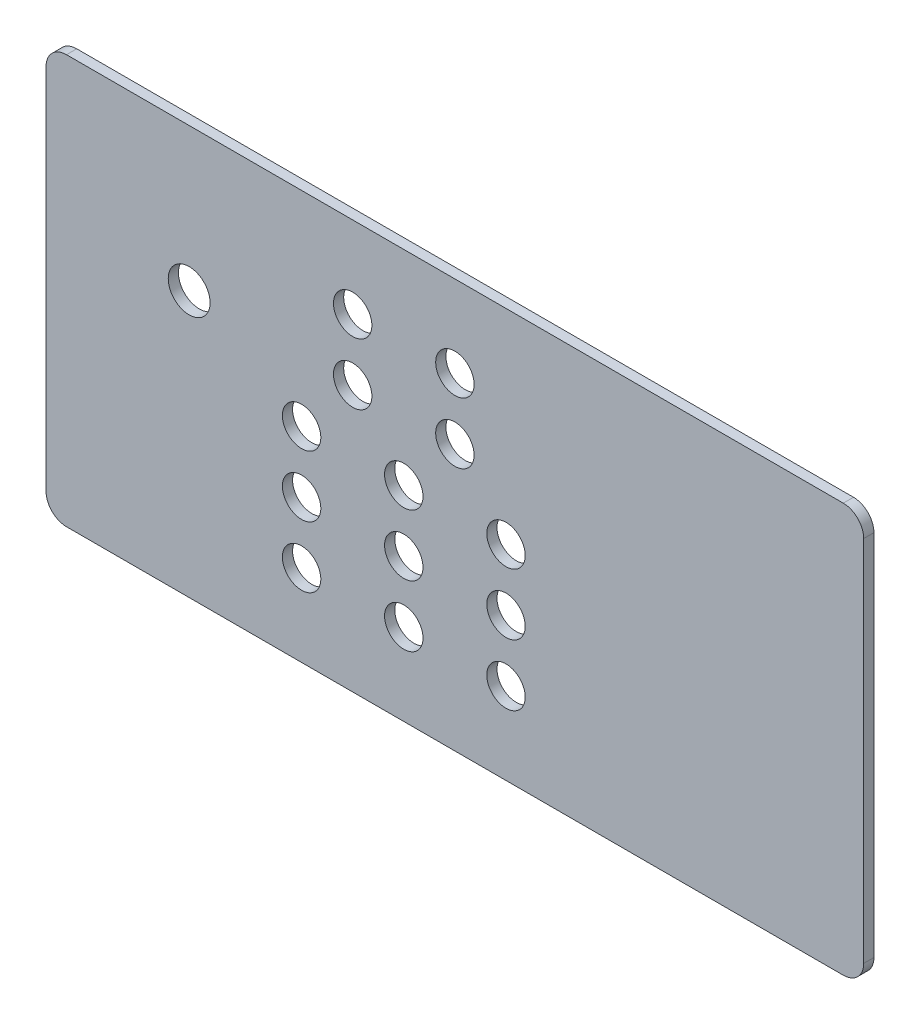
SolidWorks part; units mm, degrees
material "PC High Viscosity"
ref_plane "Front Plane" through (0, 0, 0) normal (0, 0, 1) x (1, 0, 0)
ref_plane "Top Plane" through (0, 0, 0) normal (0, 1, 0) x (1, 0, 0)
ref_plane "Right Plane" through (0, 0, 0) normal (1, 0, 0) x (0, 0, -1)
sketch "Sketch1" plane through (0, 0, 0) normal (0, 0, 1) x (1, 0, 0)
  line L1 (0, 0) -> (508, 0)
  line L2 (0, 0) -> (0, 254)
  line L3 (0, 254) -> (508, 254)
  line L4 (508, 0) -> (508, 254)
  dimension "D1" = 508
  dimension "D2" = 254
extrude "Boss-Extrude1" add sketch "Sketch1" along normal blind 6.35
sketch "Sketch3" plane through (0, 0, 0) normal (0, 0, -1) x (-1, 0, 0)
  line L0 (0, 0) -> (-508, 0) construction
  line L11 (-508, 254) -> (0, 254) construction
  line L17 (0, 254) -> (0, 0) construction
  line L18 (-508, 0) -> (-508, 254) construction
  line L19 (0, 254) -> (-25.4, 254) construction
  line L20 (0, 254) -> (0, 0) construction
  line L21 (0, 0) -> (-25.4, 0) construction
  line L22 (-25.4, 254) -> (-25.4, 0) construction
  line L23 (-508, 0) -> (-25.4, 0) construction
  line L24 (-508, 0) -> (-508, 25.4) construction
  line L25 (-508, 25.4) -> (-25.4, 25.4) construction
  line L26 (-25.4, 0) -> (-25.4, 25.4) construction
  line L27 (-508, 254) -> (-25.4, 254) construction
  line L28 (-508, 254) -> (-508, 228.6) construction
  line L29 (-508, 228.6) -> (-25.4, 228.6) construction
  line L30 (-25.4, 254) -> (-25.4, 228.6) construction
  circle A8 centre (-158.75, 88.9) radius 11.938
  circle A10 centre (-222.25, 88.9) radius 11.938
  circle A11 centre (-158.75, 50.8) radius 11.938
  circle A13 centre (-222.25, 50.8) radius 11.938
  circle A15 centre (-222.25, 127) radius 11.938
  circle A16 centre (-285.75, 127) radius 11.938
  circle A17 centre (-285.75, 88.9) radius 11.938
  circle A18 centre (-285.75, 50.8) radius 11.938
  circle A19 centre (-254, 203.2) radius 11.938
  circle A20 centre (-190.5, 203.2) radius 11.938
  circle A21 centre (-158.75, 127) radius 11.938
  circle A23 centre (-190.5, 165.1) radius 11.938
  circle A24 centre (-254, 165.1) radius 11.938
  circle A27 centre (-88.9, 165.1) radius 13
  circle A28 centre (-88.9, 165.1) radius 49.25 construction
  dimension "D2" = 23.876
  dimension "D3" = 63.5
  dimension "D4" = 38.1
  dimension "D5" = 38.1
  dimension "D6" = 63.5
  dimension "D7" = 25.4
  dimension "D8" = 38.1
  dimension "D9" = 38.1
  dimension "D10" = 25.4
  dimension "D11" = 23.876
  dimension "D12" = 63.5
  dimension "D13" = 26
  dimension "D14" = 98.5
  dimension "D15" = 31.75
  dimension "D16" = 50.8
  dimension "D17" = 25.4
  dimension "D18" = 88.9
  dimension "D19" = 88.9
  dimension "D20" = 254
extrude "Cut-Extrude2" cut sketch "Sketch3" against normal through all contours A18 | A17 | A16 | A24 | A10 | A8 | A23 | A11 | A13 | A15 | A21 | A27 | A20 | A19 region at (158.75, 88.9, 0) region at (222.25, 88.9, 0) region at (158.75, 50.8, 0) region at (222.25, 50.8, 0) region at (285.75, 127, 0) region at (285.75, 88.9, 0) region at (285.75, 50.8, 0) region at (190.5, 165.1, 0) region at (254, 165.1, 0)
fillet "Fillet1" radius 12.7 4 edges at (508, 0, 3.175) (0, 0, 3.175) (0, 254, 3.175) (508, 254, 3.175)
